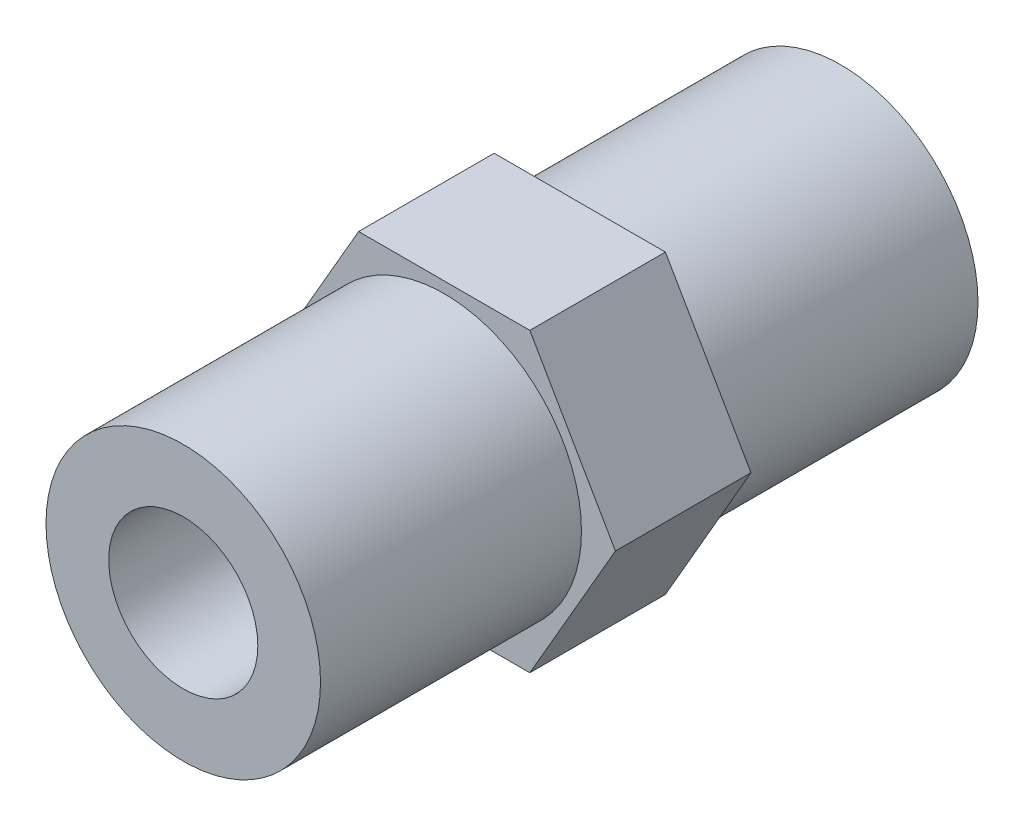
SolidWorks part; units mm, degrees
ref_plane "Front Plane" through (0, 0, 0) normal (0, 0, 1) x (1, 0, 0)
ref_plane "Top Plane" through (0, 0, 0) normal (0, 1, 0) x (1, 0, 0)
ref_plane "Right Plane" through (0, 0, 0) normal (1, 0, 0) x (0, 0, -1)
sketch "Sketch2" plane through (0, 0, 0) normal (0, 0, 1) x (1, 0, 0)
  circle A0 centre (0, 0) radius 5.1435
  dimension "D1" = 10.287
extrude "Boss-Extrude1" add sketch "Sketch2" along normal mid plane 24.638
sketch "Sketch3" plane through (0, 0, 12.319) normal (0, 0, 1) x (1, 0, 0)
  circle A0 centre (0, 0) radius 2.794
  dimension "D1" = 5.588
extrude "Cut-Extrude1" cut sketch "Sketch3" against normal through all
sketch "Sketch4" plane through (0, 0, 0) normal (0, 0, 1) x (1, 0, 0)
  line L0 (0, 0) -> (0, 5.5562) construction
  line L1 (3.2079, 5.5562) -> (-3.2079, 5.5562)
  line L2 (-3.2079, 5.5562) -> (-6.4158, 0)
  line L3 (-6.4158, 0) -> (-3.2079, -5.5563)
  line L4 (-3.2079, -5.5563) -> (3.2079, -5.5563)
  line L5 (3.2079, -5.5563) -> (6.4158, 0)
  line L6 (6.4158, 0) -> (3.2079, 5.5562)
  circle A0 centre (0, 0) radius 5.5562 construction
  dimension "D1" = 11.1125
extrude "Boss-Extrude2" add sketch "Sketch4" along normal mid plane 5.08
extrude "Cut-Extrude2" cut sketch "Sketch3<2>" against normal through all
sketch "Sketch3<2>" plane through (0, 0, 12.319) normal (0, 0, 1) x (1, 0, 0) same geometry as "Sketch3"
